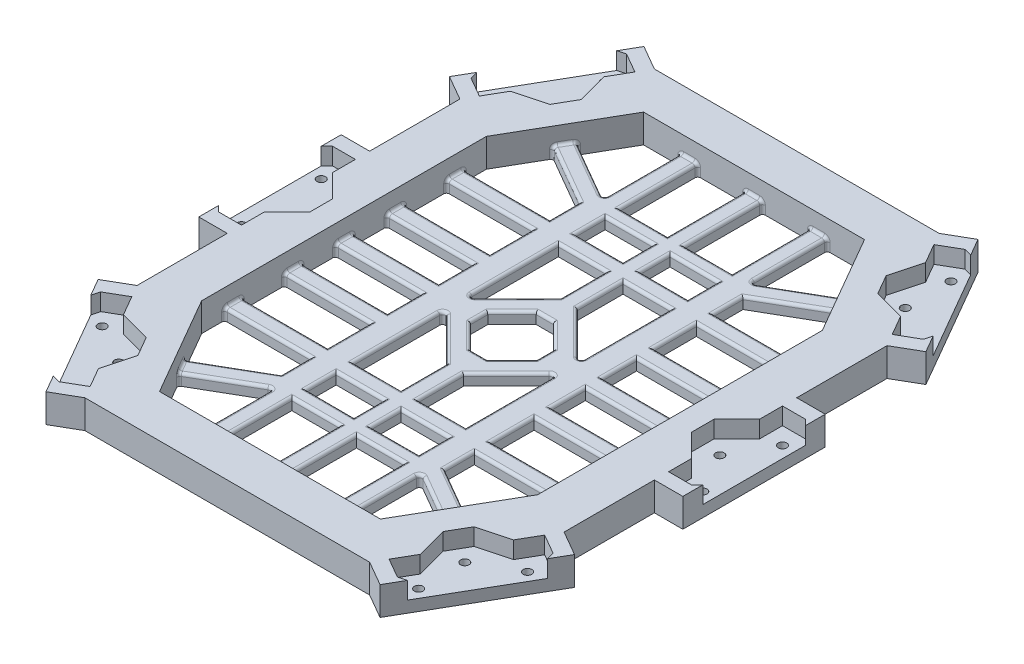
SolidWorks part; units mm, degrees
ref_plane "前视基准面" through (0, 0, 0) normal (0, 0, 1) x (1, 0, 0)
ref_plane "上视基准面" through (0, 0, 0) normal (0, 1, 0) x (1, 0, 0)
ref_plane "右视基准面" through (0, 0, 0) normal (1, 0, 0) x (0, 0, -1)
sketch "草图1" plane through (0, 0, 0) normal (0, 1, 0) x (1, 0, 0)
  line L0 (-195.8893, 0) -> (309.6729, 0) construction
  line L7 (-75, -100) -> (75, -100)
  line L8 (-75, -100) -> (-75, 100)
  line L9 (-75, 100) -> (75, 100)
  line L10 (75, -100) -> (75, 100)
  line L11 (-75, -100) -> (75, 100) construction
  line L12 (-75, 100) -> (75, -100) construction
  line L13 (0, 219.0681) -> (0, -251.4035) construction
  line L14 (50, 100) -> (75, 56.6987)
  line L15 (50, -100) -> (75, -56.6987)
  line L16 (-50, -100) -> (-75, -56.6987)
  line L17 (-50, 100) -> (-75, 56.6987)
  point P0 (0, 0)
  dimension "D1" = 200
  dimension "D2" = 150
  dimension "D3" = 30
  dimension "D4" = 25
extrude "凸台-拉伸1" add sketch "草图1" along normal blind 10 contours L9 L17 L8 L16 L7 L15 L10 L14
sketch "草图2" plane through (0, 10, 0) normal (0, 1, 0) x (1, 0, 0)
  line L0 (-102.661, 0) -> (124.4542, 0) construction
  line L1 (62.5, 78.3494) -> (89.4538, 93.9111) construction
  line L2 (50, 100) -> (75, 56.6987) construction
  line L3 (0, 121.0231) -> (0, -134.0019) construction
  line L4 (75, -56.6987) -> (75, 56.6987) construction
  line L5 (65, -25) -> (85, -25)
  line L6 (65, -25) -> (65, 25)
  line L7 (65, 25) -> (85, 25)
  line L8 (85, -25) -> (85, 25)
  line L9 (65, -25) -> (85, 25) construction
  line L10 (65, 25) -> (85, -25) construction
  line L11 (50, 100) -> (75, 56.6987)
  line L16 (50, 100) -> (58.6603, 105)
  line L17 (75, 56.6987) -> (83.6603, 61.6987)
  line L18 (58.6603, 105) -> (83.6603, 61.6987)
  line L19 (-75, 56.6987) -> (-83.6603, 61.6987)
  line L20 (-58.6603, 105) -> (-83.6603, 61.6987)
  line L21 (-50, 100) -> (-58.6603, 105)
  line L22 (-50, 100) -> (-75, 56.6987)
  line L23 (75, -56.6987) -> (83.6603, -61.6987)
  line L24 (50, -100) -> (75, -56.6987)
  line L25 (58.6603, -105) -> (83.6603, -61.6987)
  line L26 (50, -100) -> (58.6603, -105)
  line L27 (-75, -56.6987) -> (-83.6603, -61.6987)
  line L28 (-50, -100) -> (-75, -56.6987)
  line L29 (-58.6603, -105) -> (-83.6603, -61.6987)
  line L30 (-50, -100) -> (-58.6603, -105)
  line L31 (-65, -25) -> (-65, 25)
  line L32 (-65, -25) -> (-85, -25)
  line L33 (-85, -25) -> (-85, 25)
  line L34 (-65, 25) -> (-85, 25)
  point P9 (75, 0)
  dimension "D1" = 10
  dimension "D2" = 50
  dimension "D3" = 10
  dimension "D4" = 50
extrude "凸台-拉伸2" add sketch "草图2" against normal up to surface (10 mm away) up to face at (0, 0, 0)
sketch "草图3" plane through (0, 10, 0) normal (0, 1, 0) x (1, 0, 0)
  line L0 (-113.9294, 0) -> (141.0058, 0) construction
  line L1 (0, 130.5918) -> (0, -145.1714) construction
  line L2 (71.1603, 83.3494) -> (96.0895, 97.7422) construction
  line L3 (50, 100) -> (75, 56.6987) construction
  line L4 (75, 35.1529) -> (75, -48.8784) construction
  line L5 (75, 25) -> (75, 56.6987) construction
  line L6 (75, -56.6987) -> (75, -25) construction
  line L7 (67, 4) -> (67, 0)
  line L8 (67, 4) -> (75, 12)
  line L9 (75, 12) -> (75, 20)
  line L10 (75, 20) -> (83, 20)
  line L11 (83, 20) -> (88, 15)
  line L12 (88, 15) -> (88, -15)
  line L13 (67, -4) -> (67, 0)
  line L14 (67, -4) -> (75, -12)
  line L15 (75, -12) -> (75, -20)
  line L16 (75, -20) -> (83, -20)
  line L17 (83, -20) -> (88, -15)
  line L18 (83.6603, 61.6987) -> (58.6603, 105) construction
  line L19 (71.1603, 83.3494) -> (42.8499, 67.0044) construction
  line L31 (-67, -4) -> (-75, -12)
  line L32 (-75, -12) -> (-75, -20)
  line L33 (-75, -20) -> (-83, -20)
  line L34 (-83, -20) -> (-88, -15)
  line L35 (-88, 15) -> (-88, -15)
  line L36 (-83, 20) -> (-88, 15)
  line L37 (-75, 20) -> (-83, 20)
  line L38 (-75, 12) -> (-75, 20)
  line L39 (-67, 4) -> (-75, 12)
  line L40 (-67, 4) -> (-67, 0)
  line L41 (-67, -4) -> (-67, 0)
  line L75 (53.5718, 77.8135) -> (55.5718, 74.3494)
  line L76 (53.5718, 77.8135) -> (56.5, 88.7417)
  line L77 (56.5, 88.7417) -> (52.5, 95.6699)
  line L78 (52.5, 95.6699) -> (59.4282, 99.6699)
  line L79 (59.4282, 99.6699) -> (66.2583, 97.8397)
  line L80 (66.2583, 97.8397) -> (81.2583, 71.859)
  line L81 (57.5718, 70.8853) -> (55.5718, 74.3494)
  line L82 (57.5718, 70.8853) -> (68.5, 67.9571)
  line L83 (68.5, 67.9571) -> (72.5, 61.0289)
  line L84 (72.5, 61.0289) -> (79.4282, 65.0289)
  line L85 (79.4282, 65.0289) -> (81.2583, 71.859)
  line L86 (-53.5718, 77.8135) -> (-56.5, 88.7417)
  line L87 (-56.5, 88.7417) -> (-52.5, 95.6699)
  line L88 (-52.5, 95.6699) -> (-59.4282, 99.6699)
  line L89 (-59.4282, 99.6699) -> (-66.2583, 97.8397)
  line L90 (-66.2583, 97.8397) -> (-81.2583, 71.859)
  line L91 (-79.4282, 65.0289) -> (-81.2583, 71.859)
  line L92 (-72.5, 61.0289) -> (-79.4282, 65.0289)
  line L93 (-68.5, 67.9571) -> (-72.5, 61.0289)
  line L94 (-57.5718, 70.8853) -> (-68.5, 67.9571)
  line L95 (-57.5718, 70.8853) -> (-55.5718, 74.3494)
  line L96 (-53.5718, 77.8135) -> (-55.5718, 74.3494)
  line L97 (53.5718, -77.8135) -> (56.5, -88.7417)
  line L98 (56.5, -88.7417) -> (52.5, -95.6699)
  line L99 (52.5, -95.6699) -> (59.4282, -99.6699)
  line L100 (59.4282, -99.6699) -> (66.2583, -97.8397)
  line L101 (66.2583, -97.8397) -> (81.2583, -71.859)
  line L102 (79.4282, -65.0289) -> (81.2583, -71.859)
  line L103 (72.5, -61.0289) -> (79.4282, -65.0289)
  line L104 (68.5, -67.9571) -> (72.5, -61.0289)
  line L105 (57.5718, -70.8853) -> (68.5, -67.9571)
  line L106 (57.5718, -70.8853) -> (55.5718, -74.3494)
  line L107 (53.5718, -77.8135) -> (55.5718, -74.3494)
  line L108 (-53.5718, -77.8135) -> (-55.5718, -74.3494)
  line L109 (-57.5718, -70.8853) -> (-55.5718, -74.3494)
  line L110 (-57.5718, -70.8853) -> (-68.5, -67.9571)
  line L111 (-68.5, -67.9571) -> (-72.5, -61.0289)
  line L112 (-72.5, -61.0289) -> (-79.4282, -65.0289)
  line L113 (-79.4282, -65.0289) -> (-81.2583, -71.859)
  line L114 (-66.2583, -97.8397) -> (-81.2583, -71.859)
  line L115 (-59.4282, -99.6699) -> (-66.2583, -97.8397)
  line L116 (-52.5, -95.6699) -> (-59.4282, -99.6699)
  line L117 (-56.5, -88.7417) -> (-52.5, -95.6699)
  line L118 (-53.5718, -77.8135) -> (-56.5, -88.7417)
  point P33 (88, 0)
  point P39 (73.7583, 84.8494)
  point P41 (55.5718, 74.3494)
  point P56 (73.7583, 84.8494)
  dimension "D1" = 4
  dimension "D2" = 8
  dimension "D3" = 8
  dimension "D4" = 5
  dimension "D5" = 15
  dimension "D6" = 5
  dimension "D7" = 45
  dimension "D8" = 8
extrude "切除-拉伸1" cut sketch "草图3" against normal blind 6
sketch "草图4" plane through (0, 10, 0) normal (0, 1, 0) x (1, 0, 0)
  line L0 (0, 105.7312) -> (0, -113.5417) construction
  line L5 (59, 50) -> (59, -50)
  line L6 (59, 50) -> (38.7927, 85)
  line L7 (99.6564, 0) -> (-108.3347, 0) construction
  line L8 (38.7927, 85) -> (-38.7927, 85)
  line L9 (80.1603, 67.7609) -> (62.1603, 98.9378) construction
  line L10 (-50, 100) -> (50, 100) construction
  line L11 (75, 25) -> (75, 56.6987) construction
  line L12 (-59, 50) -> (-59, -50)
  line L13 (-59, 50) -> (-38.7927, 85)
  line L14 (59, -50) -> (38.7927, -85)
  line L15 (-59, -50) -> (-38.7927, -85)
  line L16 (38.7927, -85) -> (-38.7927, -85)
  point P19 (0, 85)
  point P20 (59, 0)
  point P22 (-59, 0)
  dimension "D1" = 15
  dimension "D2" = 16
  dimension "D3" = 50
extrude "切除-拉伸2" cut sketch "草图4" against normal blind 6
sketch "草图5" plane through (0, 4, 0) normal (0, 1, 0) x (1, 0, 0)
  line L0 (-113.2524, 0) -> (127.1378, 0) construction
  line L1 (0, 112.0953) -> (0, -117.8809) construction
  line L2 (48.8964, 67.5) -> (23.6793, 52.9409) construction
  line L3 (59, 50) -> (38.7927, 85) construction
  line L4 (47.3964, 70.0981) -> (25.7457, 57.5981)
  line L5 (28.7457, 52.4019) -> (25.7457, 57.5981)
  line L6 (50.3964, 64.9019) -> (28.7457, 52.4019)
  line L7 (59, 50) -> (38.7927, 85) construction
  line L8 (25.7457, 57.5981) -> (25.7457, 85)
  line L9 (-47.3964, -70.0981) -> (-25.7457, -57.5981)
  line L10 (38.7927, 85) -> (-38.7927, 85) construction
  line L11 (25.7457, 57.5981) -> (19.7457, 57.5981)
  line L12 (19.7457, 57.5981) -> (19.7457, 85)
  line L13 (38.7927, 85) -> (-38.7927, 85) construction
  line L14 (3, 85) -> (3, 20)
  line L15 (3, 20) -> (20, 3)
  line L16 (20, 3) -> (59, 3)
  line L17 (59, -50) -> (59, 50) construction
  line L18 (-3, 11.5147) -> (3, 11.5147)
  line L19 (3, 11.5147) -> (11.5147, 3)
  line L20 (11.5147, 3) -> (11.5147, -3)
  line L21 (19.7457, 57.5981) -> (3, 57.5981)
  line L22 (28.7457, 52.4019) -> (3, 52.5)
  line L23 (28.7457, 52.4019) -> (28.7457, 36)
  line L24 (28.7457, 36) -> (59, 36)
  line L25 (59, 42) -> (28.7457, 42)
  line L26 (59, -50) -> (59, 50) construction
  line L27 (28.7457, 36) -> (28.7457, 21)
  line L28 (28.7457, 21) -> (59, 21)
  line L29 (59, 36) -> (59, 42)
  line L30 (59, 21) -> (59, 15)
  line L31 (59, 15) -> (28.7457, 15)
  line L32 (28.7457, 15) -> (28.7457, 21)
  line L33 (28.7457, 15) -> (28.7457, 3)
  line L34 (19.7457, 57.5981) -> (19.7457, 3.2543)
  line L35 (28.7457, 42) -> (3, 42)
  line L36 (28.7457, 36) -> (3, 36)
  line L37 (-20, 3) -> (-59, 3)
  line L38 (-59, 15) -> (-28.7457, 15)
  line L39 (-28.7457, 21) -> (-59, 21)
  line L40 (-28.7457, 36) -> (-59, 36)
  line L41 (-59, 42) -> (-28.7457, 42)
  line L42 (-3, 85) -> (-3, 20)
  line L43 (-25.7457, 57.5981) -> (-25.7457, 85)
  line L44 (-19.7457, 57.5981) -> (-19.7457, 85)
  line L45 (-28.7457, 36) -> (-3, 36)
  line L46 (-28.7457, 42) -> (-3, 42)
  line L47 (-19.7457, 57.5981) -> (-19.7457, 3.2543)
  line L48 (-28.7457, 15) -> (-28.7457, 3)
  line L49 (-28.7457, 15) -> (-28.7457, 21)
  line L50 (-28.7457, 36) -> (-28.7457, 21)
  line L51 (-28.7457, 52.4019) -> (-28.7457, 36)
  line L52 (-28.7457, 52.4019) -> (-3, 52.5)
  line L53 (-19.7457, 57.5981) -> (-3, 57.5981)
  line L54 (-11.5147, 3) -> (-11.5147, -3)
  line L55 (-3, 11.5147) -> (-11.5147, 3)
  line L56 (-3, 20) -> (-20, 3)
  line L57 (-25.7457, 57.5981) -> (-19.7457, 57.5981)
  line L58 (-50.3964, 64.9019) -> (-28.7457, 52.4019)
  line L59 (-28.7457, 52.4019) -> (-25.7457, 57.5981)
  line L60 (-47.3964, 70.0981) -> (-25.7457, 57.5981)
  line L61 (-28.7457, -52.4019) -> (-25.7457, -57.5981)
  line L62 (-50.3964, -64.9019) -> (-28.7457, -52.4019)
  line L63 (-25.7457, -57.5981) -> (-19.7457, -57.5981)
  line L64 (-3, -20) -> (-20, -3)
  line L65 (-3, -11.5147) -> (-11.5147, -3)
  line L66 (-19.7457, -57.5981) -> (-3, -57.5981)
  line L67 (-28.7457, -52.4019) -> (-3, -52.5)
  line L68 (-28.7457, -52.4019) -> (-28.7457, -36)
  line L69 (-28.7457, -36) -> (-28.7457, -21)
  line L70 (-28.7457, -15) -> (-28.7457, -21)
  line L71 (-28.7457, -15) -> (-28.7457, -3)
  line L72 (-19.7457, -57.5981) -> (-19.7457, -3.2543)
  line L73 (-28.7457, -42) -> (-3, -42)
  line L74 (-28.7457, -36) -> (-3, -36)
  line L75 (-19.7457, -57.5981) -> (-19.7457, -85)
  line L76 (-25.7457, -57.5981) -> (-25.7457, -85)
  line L77 (-3, -85) -> (-3, -20)
  line L78 (-59, -42) -> (-28.7457, -42)
  line L79 (-28.7457, -36) -> (-59, -36)
  line L80 (-28.7457, -21) -> (-59, -21)
  line L81 (-59, -15) -> (-28.7457, -15)
  line L82 (-20, -3) -> (-59, -3)
  line L83 (28.7457, -36) -> (3, -36)
  line L84 (28.7457, -42) -> (3, -42)
  line L85 (19.7457, -57.5981) -> (19.7457, -3.2543)
  line L86 (28.7457, -15) -> (28.7457, -3)
  line L87 (28.7457, -15) -> (28.7457, -21)
  line L88 (59, -15) -> (28.7457, -15)
  line L89 (59, -21) -> (59, -15)
  line L90 (59, -36) -> (59, -42)
  line L91 (28.7457, -21) -> (59, -21)
  line L92 (28.7457, -36) -> (28.7457, -21)
  line L93 (59, -42) -> (28.7457, -42)
  line L94 (28.7457, -36) -> (59, -36)
  line L95 (28.7457, -52.4019) -> (28.7457, -36)
  line L96 (28.7457, -52.4019) -> (3, -52.5)
  line L97 (19.7457, -57.5981) -> (3, -57.5981)
  line L98 (3, -11.5147) -> (11.5147, -3)
  line L99 (-3, -11.5147) -> (3, -11.5147)
  line L100 (20, -3) -> (59, -3)
  line L101 (3, -20) -> (20, -3)
  line L102 (3, -85) -> (3, -20)
  line L103 (19.7457, -57.5981) -> (19.7457, -85)
  line L104 (25.7457, -57.5981) -> (19.7457, -57.5981)
  line L105 (25.7457, -57.5981) -> (25.7457, -85)
  line L106 (50.3964, -64.9019) -> (28.7457, -52.4019)
  line L107 (28.7457, -52.4019) -> (25.7457, -57.5981)
  line L108 (47.3964, -70.0981) -> (25.7457, -57.5981)
  point P13 (27.2457, 55)
  point P75 (0, 11.5147)
  point P86 (-11.5147, 0)
  point P121 (11.5147, 0)
  line M28 (59, 50) -> (38.7927, 85)
  line M29 (38.7927, 85) -> (-38.7927, 85)
  line M30 (-38.7927, 85) -> (-59, 50)
  line M31 (-59, 50) -> (-59, -50)
  line M32 (-59, -50) -> (-38.7927, -85)
  line M33 (-38.7927, -85) -> (38.7927, -85)
  line M34 (38.7927, -85) -> (59, -50)
  line M35 (59, -50) -> (59, 50)
  dimension "D1" = 6
  dimension "D2" = 25
  dimension "D3" = 6
  dimension "D4" = 3
  dimension "D5" = 3
  dimension "D6" = 45
  dimension "D7" = 65
  dimension "D8" = 6
  dimension "D9" = 3
  dimension "D10" = 3
  dimension "D11" = 6
  dimension "D12" = 6
  dimension "D13" = 12
  dimension "D14" = 15
extrude "切除-拉伸3" cut sketch "草图5" against normal blind 4 contours L60 L43 M30 M29 | L44 L53 L42 M29 | L21 L12 L14 M29 | L8 L4 M28 M29 | L25 L6 L23 M35 M28 | L58 L41 L51 M30 M31 | L52 L47 L46 L42 | L35 L34 L22 L14 | L50 L40 L39 M31 | L48 L38 L37 M31 | L71 L82 L81 M31 | L56 L42 L45 L47 | L34 L36 L14 L15 | L27 L28 L24 M35 | L65 L99 L98 L20 L19 L18 L55 L54 | L31 L33 L16 M35 | L100 L86 L88 M35 | L92 L94 L91 M35 | L69 L80 L79 M31 | L74 L77 L64 L72 | L102 L83 L85 L101 | L106 L93 L95 M34 M35 | L102 L96 L85 L84 | L103 L97 L102 M33 | L108 L105 M34 M33 | L77 L66 L75 M33 | L67 L77 L73 L72 | L78 L62 L68 M31 M32 | L76 L9 M32 M33
fillet "圆角1" radius 1 114 edges at (-59, 2, -21) (-59, 2, -36) (-59, 2, -42) (-25.7457, 2, -85) (-19.7457, 2, -85) (-3, 2, -85) (3, 2, -85) (25.7457, 2, -85) (50.3964, 2, -64.9019) (59, 2, -42) (59, 2, -21) (59, 2, -3) (59, 2, 3) (59, 2, 15) (59, 2, 21) (50.3964, 2, 64.9019) (47.3964, 2, 70.0981) (25.7457, 2, 85) (19.7457, 2, 85) (-3, 2, 85) (-47.3964, 2, 70.0981) (-50.3964, 2, 64.9019) (-59, 2, 42) (-59, 2, 36) (-59, 2, 15) (-59, 2, 3) (-59, 2, -3) (-59, 2, -15) (-43.8729, 4, -36) (-59, 4, -39) (-43.8729, 4, -42) (-39.5711, 4, -58.6519) (-48.8964, 4, -67.5) (-36.5711, 4, -63.8481) (-25.7457, 4, -71.299) (-22.7457, 4, -85) (-19.7457, 4, -71.299) (-3, 4, -71.299) (0, 4, -85) (3, 4, -71.299) (11.3729, 4, -57.5981) (19.7457, 4, -71.299) (22.7457, 4, -85) (36.5711, 4, -63.8481) (48.8964, 4, -67.5) (28.7457, 4, -47.201) (43.8729, 4, -36) (43.8729, 4, -21) (59, 4, -18) (28.7457, 4, -9) (59, 4, 0) (43.8729, 4, 3) (28.7457, 4, 9) (43.8729, 4, 15) (43.8729, 4, 21) (43.8729, 4, 36) (59, 4, 39) (43.8729, 4, 42) (39.5711, 4, 58.6519) (25.7457, 4, 71.299) (22.7457, 4, 85) (19.7457, 4, 71.299) (11.3729, 4, 57.5981) (3, 4, 71.299) (0, 4, 85) (-3, 4, 71.299) (-11.3729, 4, 57.5981) (-19.7457, 4, 71.299) (-36.5711, 4, 63.8481) (-28.7457, 4, 47.201) (-43.8729, 4, 36) (-28.7457, 4, 28.5) (-43.8729, 4, 21) (-59, 4, 18) (-43.8729, 4, 15) (-28.7457, 4, 9) (-43.8729, 4, 3) (-59, 4, 0) (-28.7457, 4, -9) (-43.8729, 4, -15) (-59, 4, -18) (-11.3729, 4, -11.6271) (-3, 4, -28) (3, 4, -28) (19.7457, 4, -19.6271) (11.3729, 4, -36) (0, 4, -11.5147) (-7.2574, 4, -7.2574) (-11.5147, 4, 0) (-7.2574, 4, 7.2574) (11.3729, 4, -52.4681) (3, 4, -47.25) (11.3729, 4, -42) (-11.3729, 4, -42) (-3, 4, -47.25) (-11.3729, 4, -52.4681) (19.7457, 4, 47.2181) (11.3729, 4, 42) (3, 4, 47.25) (11.3729, 4, 52.4681) (11.3729, 4, 36) (-3, 4, 28) (-11.3729, 4, 11.6271) (-3, 4, 47.25) (-11.3729, 4, 42) (-11.3729, 4, 52.4681) (25.7457, 2, -57.5981) (-25.7457, 2, -57.5981) (-25.7457, 2, 57.5981) (25.7457, 2, 57.5981) (19.7457, 2, 3.2543) (-19.7457, 2, 3.2543) (-19.7457, 2, -3.2543) (19.7457, 2, -3.2543)
sketch "草图6" plane through (0, 4, 0) normal (0, 1, 0) x (1, 0, 0)
  line L0 (-101.1028, 0) -> (114.9881, 0) construction
  line L1 (0, 108.624) -> (0, -112.6739) construction
  line L2 (67, 4) -> (67, -4) construction
  line L3 (83, 20) -> (75, 20) construction
  line L4 (75, 20) -> (75, 12) construction
  line L5 (71.1603, 83.3494) -> (49.8215, 71.0294) construction
  line L6 (80.1603, 67.7609) -> (62.1603, 98.9378) construction
  line L7 (53.5718, 77.8135) -> (57.5718, 70.8853) construction
  line L8 (52.5, 95.6699) -> (56.5, 88.7417) construction
  line L9 (59.4282, 99.6699) -> (52.5, 95.6699) construction
  line L10 (72.5, 61.0289) -> (79.4282, 65.0289) construction
  circle A0 centre (73, 0) radius 1.5
  circle A1 centre (81, 14) radius 1.5
  circle A2 centre (81, -14) radius 1.5
  circle A3 centre (60.7679, 77.3494) radius 1.5
  circle A4 centre (60.6962, 93.4737) radius 1.5
  circle A5 centre (74.6962, 69.225) radius 1.5
  circle A6 centre (-81, -14) radius 1.5
  circle A7 centre (-73, 0) radius 1.5
  circle A8 centre (-81, 14) radius 1.5
  circle A9 centre (-74.6962, 69.225) radius 1.5
  circle A10 centre (-60.7679, 77.3494) radius 1.5
  circle A11 centre (-60.6962, 93.4737) radius 1.5
  circle A12 centre (-74.6962, -69.225) radius 1.5
  circle A13 centre (-60.7679, -77.3494) radius 1.5
  circle A14 centre (-60.6962, -93.4737) radius 1.5
  circle A15 centre (74.6962, -69.225) radius 1.5
  circle A16 centre (60.7679, -77.3494) radius 1.5
  circle A17 centre (60.6962, -93.4737) radius 1.5
  dimension "D1" = 3
  dimension "D2" = 3
  dimension "D4" = 6
  dimension "D5" = 6
  dimension "D6" = 3
  dimension "D7" = 3
  dimension "D9" = 6
  dimension "D10" = 6
  dimension "D3" = 6
  dimension "D8" = 6
extrude "切除-拉伸4" cut sketch "草图6" against normal through all
